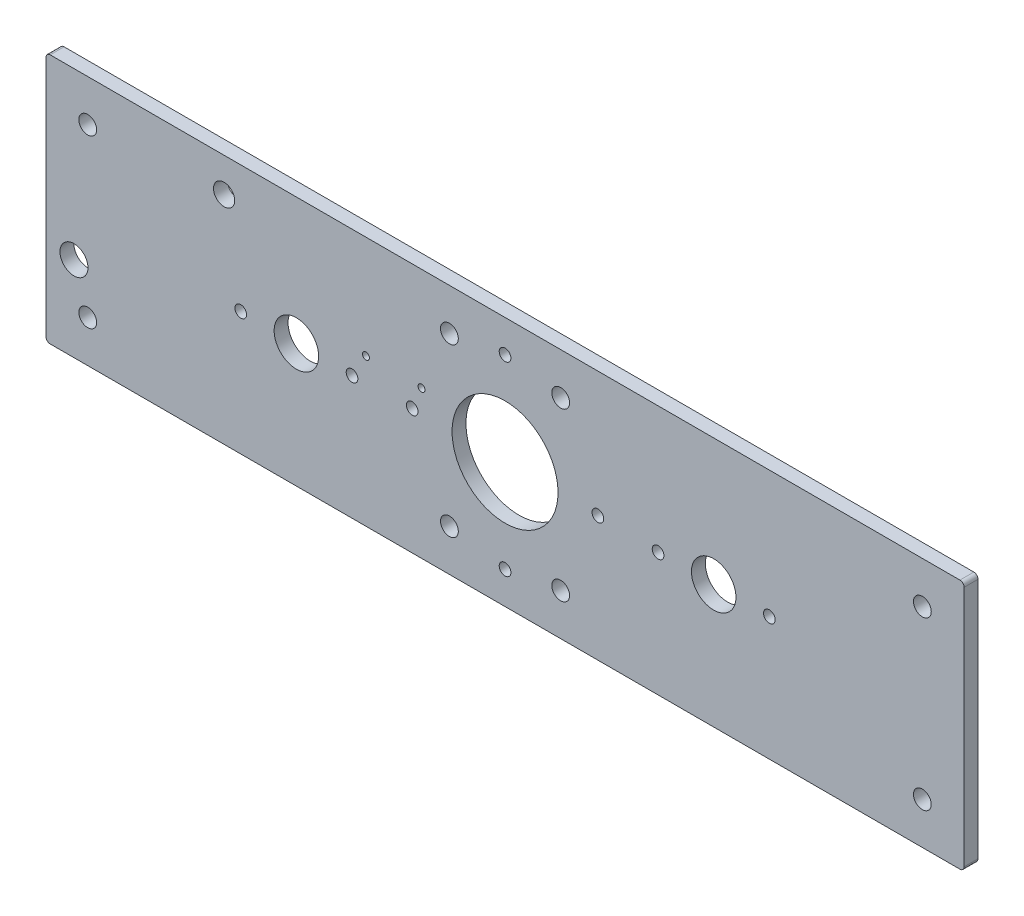
SolidWorks part; units mm, degrees
ref_plane "Front Plane" through (0, 0, 0) normal (0, 0, 1) x (1, 0, 0)
ref_plane "Top Plane" through (0, 0, 0) normal (0, 1, 0) x (1, 0, 0)
ref_plane "Right Plane" through (0, 0, 0) normal (1, 0, 0) x (0, 0, -1)
sketch "Sketch1" plane through (0, 0, 0) normal (0, 0, 1) x (1, 0, 0)
  line L1 (165, -45) -> (-165, -45)
  line L2 (165, -45) -> (165, 45)
  line L3 (165, 45) -> (-165, 45)
  line L4 (-165, -45) -> (-165, 45)
  line L5 (165, -45) -> (-165, 45) construction
  line L6 (165, 45) -> (-165, -45) construction
  circle A0 centre (0, 0) radius 19.05
  point P0 (0, 0)
  dimension "D3" = 38.1
  dimension "D1" = 90
  dimension "D2" = 330
extrude "Boss-Extrude1" add sketch "Sketch1" along normal mid plane 5
hole_wizard "M6 Clearance Hole1" positions "Sketch5" profile "Sketch4" hole size "M6" standard "ANSI Metric" end condition through all
sketch "Sketch5" plane through (0, 0, 2.5) normal (0, 0, 1) x (1, 0, 0)
  line L0 (165, 45) -> (-165, 45) construction
  line L1 (-165, 45) -> (-165, -45) construction
  line L2 (-165, -45) -> (165, -45) construction
  point P0 (-150, 30)
  point P2 (-20, 30)
  point P4 (-20, -30)
  point P6 (-150, -30)
  dimension "D1" = 15
  dimension "D2" = 20
  dimension "D3" = 15
  dimension "D4" = 15
  dimension "D5" = 15
  dimension "D6" = 15
  dimension "D7" = 15
  dimension "D8" = 20
sketch "Sketch4" plane through (-150, 30, 2.5) normal (1, 0, 0) x (0, -1, 0)
  line L0 (0, 0) -> (0, 5)
  line L1 (0, 5) -> (3.2, 5)
  line L2 (3.2, 5) -> (3.2, 0)
  line L5 (3.2, 0) -> (0, 0)
  line L11 (0, -6.35) -> (0, 107.95) construction
  dimension "Thru Hole Dia." = 6.4
  dimension "Thru Hole Depth" = 5
mirror "Mirror2" about plane through (0, 0, 0) normal (1, 0, 0) of "M6 Clearance Hole1"
sketch "Sketch3" plane through (0, 0, 2.5) normal (0, 0, 1) x (1, 0, 0)
  line L0 (0, -0.6) -> (-49.4534, -0.6) construction
  circle A2 centre (-75, -0.6) radius 8
  dimension "D3" = 16
  dimension "D4" = 75
  dimension "D7" = 0.6
extrude "Cut-Extrude2" cut sketch "Sketch3" against normal through all
hole_wizard "M5x0.8 Tapped Hole1" positions "Sketch7" profile "Sketch6" tap size "M5x0.8" standard "ANSI Metric" end condition through all
sketch "Sketch7" plane through (0, 0, 2.5) normal (0, 0, 1) x (1, 0, 0)
  line L0 (-1080, -0.6) -> (48920, -0.6) construction
  circle A0 centre (-75, -0.6) radius 8 construction
  point P0 (-95, -0.6)
  point P2 (-55, -0.6)
  dimension "D1" = 20
  dimension "D2" = 20
sketch "Sketch6" plane through (-95, -0.6, 2.5) normal (1, 0, 0) x (0, -1, 0)
  line L0 (0, 0) -> (0, 5)
  line L1 (0, 5) -> (2.1, 5)
  line L2 (2.1, 5) -> (2.1, 0)
  line L5 (2.1, 0) -> (0, 0)
  line L11 (0, -6.35) -> (0, 107.95) construction
  dimension "Thru Tap Drill Dia." = 4.2
  dimension "Thru Tap Drill Depth" = 5
cosmetic thread "Hole Thread1" parameters "D2"=5
cosmetic thread "Hole Thread2" parameters "D2"=5
mirror "Mirror1" about plane through (0, 0, 0) normal (1, 0, 0) of "M5x0.8 Tapped Hole1", "Cut-Extrude2"
hole_wizard "M5x0.8 Tapped Hole3" positions "Sketch9" profile "Sketch8" tap size "M5x0.8" standard "ANSI Metric" end condition through all
sketch "Sketch9" plane through (0, 0, 2.5) normal (0, 0, 1) x (1, 0, 0)
  line L1 (0, -33.3754) -> (33.3754, 0) construction
  line L2 (0, -33.3754) -> (-33.3754, 0) construction
  line L3 (-33.3754, 0) -> (0, 33.3754) construction
  line L4 (33.3754, 0) -> (0, 33.3754) construction
  line L5 (0, -33.3754) -> (0, 33.3754) construction
  line L6 (-33.3754, 0) -> (33.3754, 0) construction
  line L7 (-1000, 0) -> (49000, 0) construction
  point P1 (0, 33.3754)
  point P164 (0, -33.3754)
  point P165 (-33.3754, 0)
  point P166 (33.3754, 0)
  dimension "D1" = 47.2
  dimension "D2" = 47.2
  dimension "D3" = 90
  dimension "D4" = 90
  dimension "D5" = 90
  dimension "D6" = 90
  dimension "D7" = 23.6
  dimension "D8" = 23.6
sketch "Sketch8" plane through (0, 33.3754, 2.5) normal (1, 0, 0) x (0, -1, 0)
  line L0 (0, 0) -> (0, 5)
  line L1 (0, 5) -> (2.1, 5)
  line L2 (2.1, 5) -> (2.1, 0)
  line L5 (2.1, 0) -> (0, 0)
  line L11 (0, -6.35) -> (0, 107.95) construction
  dimension "Thru Tap Drill Dia." = 4.2
  dimension "Thru Tap Drill Depth" = 5
cosmetic thread "Hole Thread3" parameters "D2"=5
cosmetic thread "Hole Thread4" parameters "D2"=5
cosmetic thread "Hole Thread5" parameters "D2"=5
cosmetic thread "Hole Thread6" parameters "D2"=5
fillet "Fillet1" radius 1.5 4 edges at (-165, -45, 0) (165, -45, 0) (165, 45, 0) (-165, 45, 0)
hole_wizard "M3x0.5 Tapped Hole1" positions "Sketch12" profile "Sketch11" tap size "M3x0.5" standard "ANSI Metric" end condition through all
sketch "Sketch12" plane through (0, 0, 2.5) normal (0, 0, 1) x (1, 0, 0)
  line L0 (-50, 8) -> (-30, 8)
  point P0 (-50, 8)
  point P2 (-30, 8)
  dimension "D1" = 20
  dimension "D2" = 8
  dimension "D3" = 30
sketch "Sketch11" plane through (-50, 8, 2.5) normal (1, 0, 0) x (0, -1, 0)
  line L0 (0, 0) -> (0, 5)
  line L1 (0, 5) -> (1.25, 5)
  line L2 (1.25, 5) -> (1.25, 0)
  line L5 (1.25, 0) -> (0, 0)
  line L11 (0, -6.35) -> (0, 107.95) construction
  dimension "Thru Tap Drill Dia." = 2.5
  dimension "Thru Tap Drill Depth" = 5
cosmetic thread "Hole Thread7" parameters "D2"=3
cosmetic thread "Hole Thread8" parameters "D2"=3
sketch "Sketch13" plane through (0, 0, 2.5) normal (0, 0, 1) x (1, 0, 0)
  circle A0 centre (-100.9899, 32.7821) radius 3.8128
extrude "Cut-Extrude3" cut sketch "Sketch13" against normal through all
sketch "Sketch14" plane through (0, 0, 2.5) normal (0, 0, 1) x (1, 0, 0)
  circle A0 centre (-154.9448, -14.5073) radius 5.0278
extrude "Cut-Extrude4" cut sketch "Sketch14" against normal blind 10
equation "\"D4@Sketch3\"=150/2"
